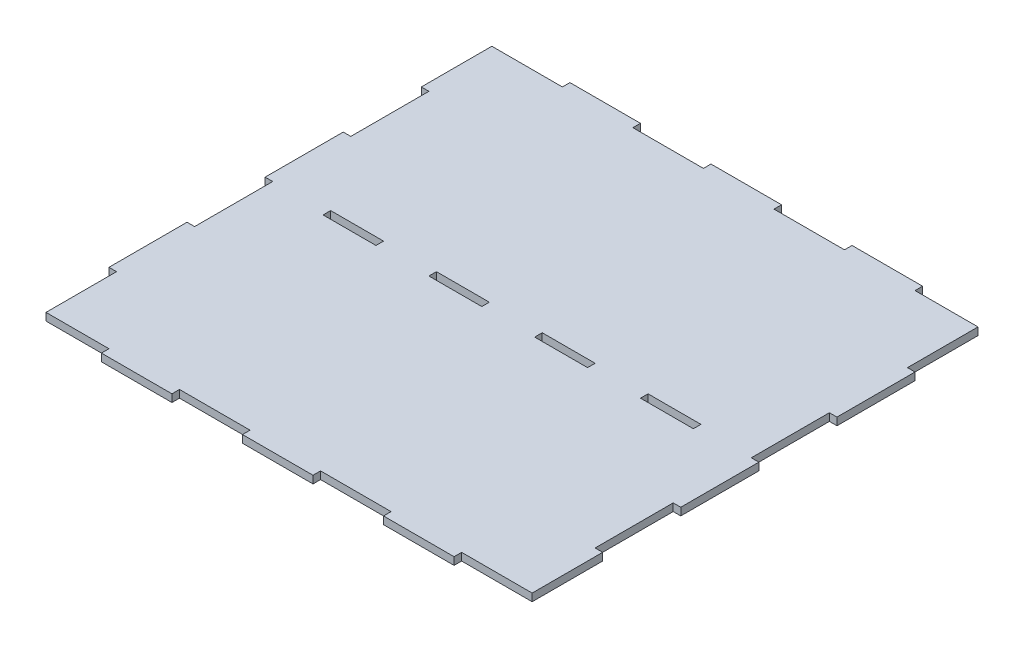
SolidWorks part; units mm, degrees
ref_plane "Front Plane" through (0, 0, 0) normal (0, 0, 1) x (1, 0, 0)
ref_plane "Top Plane" through (0, 0, 0) normal (0, 1, 0) x (1, 0, 0)
ref_plane "Right Plane" through (0, 0, 0) normal (1, 0, 0) x (0, 0, -1)
sketch "Sketch1" plane through (0, 0, 0) normal (0, 1, 0) x (1, 0, 0)
  line L0 (-98, -90) -> (-70, -90)
  line L1 (-98, -93) -> (98, -93)
  line L2 (-98, -93) -> (-98, 93)
  line L3 (-98, 93) -> (98, 93)
  line L4 (98, -93) -> (98, 93)
  line L5 (-98, -93) -> (98, 93) construction
  line L6 (-98, 93) -> (98, -93) construction
  line L7 (-70, -90) -> (-70, -93)
  line L8 (-70, -93) -> (-42, -93)
  line L9 (-42, -93) -> (-42, -90)
  line L10 (-42, -90) -> (-14, -90)
  line L11 (-14, -90) -> (-14, -93)
  line L12 (-14, -93) -> (14, -93)
  line L13 (14, -93) -> (14, -90)
  line L14 (14, -90) -> (42, -90)
  line L15 (42, -90) -> (42, -93)
  line L16 (42, -93) -> (70, -93)
  line L17 (70, -93) -> (70, -90)
  line L18 (70, -90) -> (98, -90)
  line L19 (-98, 90) -> (-70, 90)
  line L20 (-70, 90) -> (-70, 93)
  line L21 (-70, 93) -> (-42, 93)
  line L22 (-42, 93) -> (-42, 90)
  line L23 (-42, 90) -> (-14, 90)
  line L24 (-14, 90) -> (-14, 93)
  line L25 (-14, 93) -> (14, 93)
  line L26 (14, 93) -> (14, 90)
  line L27 (14, 90) -> (42, 90)
  line L28 (42, 90) -> (42, 93)
  line L29 (42, 93) -> (70, 93)
  line L30 (70, 93) -> (70, 90)
  line L31 (70, 90) -> (98, 90)
  line L32 (-98, -93) -> (-95, -93)
  line L33 (-95, -93) -> (-95, -62)
  line L34 (-95, -62) -> (-98, -62)
  line L35 (-98, -62) -> (-98, -31)
  line L36 (-98, -31) -> (-95, -31)
  line L37 (-95, -31) -> (-95, 0)
  line L38 (-95, 0) -> (-98, 0)
  line L39 (-98, 0) -> (-98, 31)
  line L40 (-98, 31) -> (-95, 31)
  line L41 (-95, 31) -> (-95, 62)
  line L42 (-95, 62) -> (-98, 62)
  line L43 (98, -62) -> (95, -62)
  line L44 (95, -62) -> (95, -31)
  line L45 (95, -31) -> (98, -31)
  line L46 (98, -31) -> (98, 0)
  line L47 (98, 0) -> (95, 0)
  line L48 (95, 0) -> (95, 31)
  line L49 (95, 31) -> (98, 31)
  line L50 (98, 31) -> (98, 62)
  line L51 (98, 62) -> (95, 62)
  line L52 (95, 62) -> (95, 93)
  line L54 (-10.5, -1.5) -> (-31.5, -1.5)
  line L55 (-10.5, -1.5) -> (-10.5, 1.5)
  line L56 (-10.5, 1.5) -> (-31.5, 1.5)
  line L57 (-31.5, -1.5) -> (-31.5, 1.5)
  line L58 (-10.5, -1.5) -> (-31.5, 1.5) construction
  line L59 (-10.5, 1.5) -> (-31.5, -1.5) construction
  line L60 (-73.5, 1.5) -> (-52.5, 1.5)
  line L61 (-73.5, 1.5) -> (-73.5, -1.5)
  line L62 (-73.5, -1.5) -> (-52.5, -1.5)
  line L63 (-52.5, 1.5) -> (-52.5, -1.5)
  line L64 (-73.5, 1.5) -> (-52.5, -1.5) construction
  line L65 (-73.5, -1.5) -> (-52.5, 1.5) construction
  line L66 (10.5, -1.5) -> (31.5, -1.5)
  line L67 (10.5, -1.5) -> (10.5, 1.5)
  line L68 (10.5, 1.5) -> (31.5, 1.5)
  line L69 (31.5, -1.5) -> (31.5, 1.5)
  line L70 (10.5, -1.5) -> (31.5, 1.5) construction
  line L71 (10.5, 1.5) -> (31.5, -1.5) construction
  line L72 (52.5, -1.5) -> (73.5, -1.5)
  line L73 (52.5, -1.5) -> (52.5, 1.5)
  line L74 (52.5, 1.5) -> (73.5, 1.5)
  line L75 (73.5, -1.5) -> (73.5, 1.5)
  line L76 (52.5, -1.5) -> (73.5, 1.5) construction
  line L77 (52.5, 1.5) -> (73.5, -1.5) construction
  point P0 (0, 0)
  point P47 (-21, 0)
  point P61 (-63, 0)
  point P66 (21, 0)
  point P71 (63, 0)
  dimension "D1" = 196
  dimension "D2" = 186
  dimension "D3" = 28
  dimension "D4" = 28
  dimension "D5" = 28
  dimension "D6" = 28
  dimension "D7" = 28
  dimension "D8" = 28
  dimension "D9" = 3
  dimension "D10" = 3
  dimension "D11" = 3
  dimension "D12" = 3
  dimension "D13" = 3
  dimension "D14" = 3
  dimension "D15" = 3
  dimension "D16" = 3
  dimension "D17" = 31
  dimension "D18" = 31
  dimension "D19" = 31
  dimension "D20" = 31
  dimension "D21" = 31
  dimension "D22" = 3
  dimension "D23" = 3
  dimension "D24" = 3
  dimension "D25" = 3
  dimension "D26" = 31
  dimension "D27" = 31
  dimension "D28" = 31
  dimension "D29" = 31
  dimension "D30" = 21
  dimension "D31" = 21
  dimension "D32" = 21
  dimension "D33" = 21
  dimension "D34" = 3
  dimension "D35" = 3
  dimension "D36" = 3
  dimension "D37" = 3
  dimension "D38" = 0
  dimension "D39" = 0
  dimension "D40" = 0
  dimension "D41" = 0
  dimension "D42" = 10.5
  dimension "D43" = 10.5
  dimension "D44" = 21
  dimension "D45" = 21
extrude "Boss-Extrude1" add sketch "Sketch1" along normal blind 3 contours L31 L30 L3 L28 L27 L26 L24 L23 L22 L20 L19 L2 L0 L7 L1 L9 L10 L11 L13 L14 L15 L17 L18 L4 region at (0, 0, 0)
